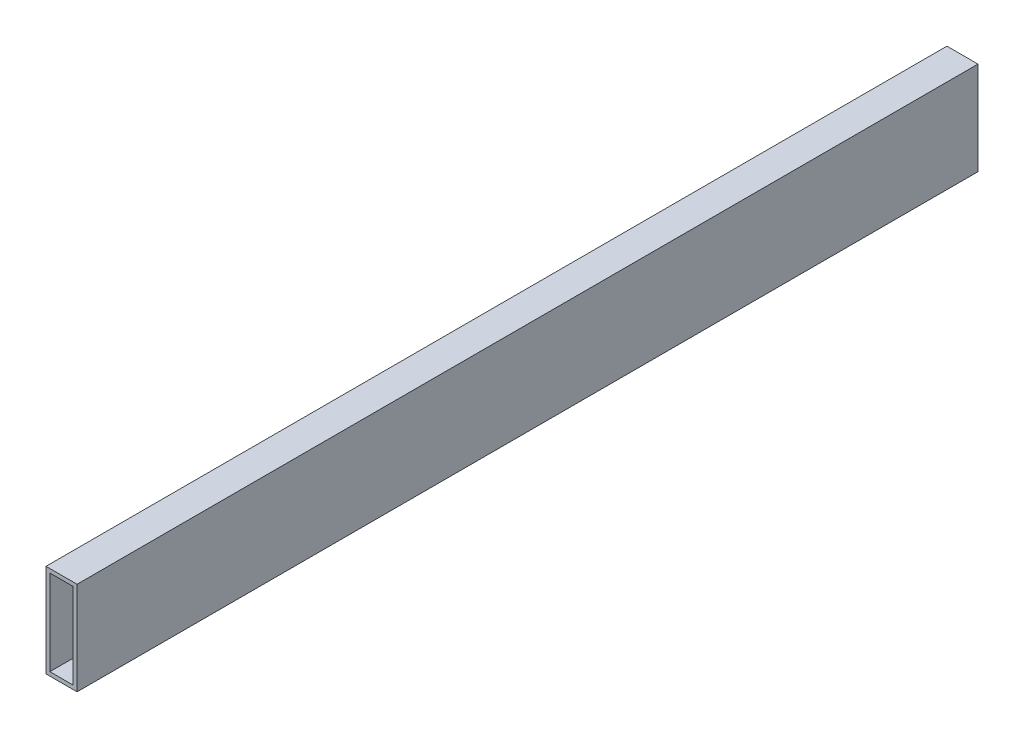
SolidWorks part; units mm, degrees
ref_plane "Front Plane" through (0, 0, 0) normal (0, 0, 1) x (1, 0, 0)
ref_plane "Top Plane" through (0, 0, 0) normal (0, 1, 0) x (1, 0, 0)
ref_plane "Right Plane" through (0, 0, 0) normal (1, 0, 0) x (0, 0, -1)
sketch "Sketch1" plane through (0, 0, 0) normal (0, 0, 1) x (1, 0, 0)
  line L1 (-12.7, -38.1) -> (12.7, -38.1)
  line L2 (-12.7, -38.1) -> (-12.7, 38.1)
  line L3 (-12.7, 38.1) -> (12.7, 38.1)
  line L4 (12.7, -38.1) -> (12.7, 38.1)
  line L5 (-12.7, -38.1) -> (12.7, 38.1) construction
  line L6 (-12.7, 38.1) -> (12.7, -38.1) construction
  point P0 (0, 0)
  dimension "D1" = 25.4
  dimension "D2" = 76.2
extrude "Boss-Extrude1" add sketch "Sketch1" along normal mid plane 736.6
shell "Shell1" thickness 3.175 removed face at (0, 0, -368.3) removed face at (0, 0, 368.3)
equation "\"robotwidth\"= 29in"
equation "\"D1@Boss-Extrude1\"=\"robotwidth\""
